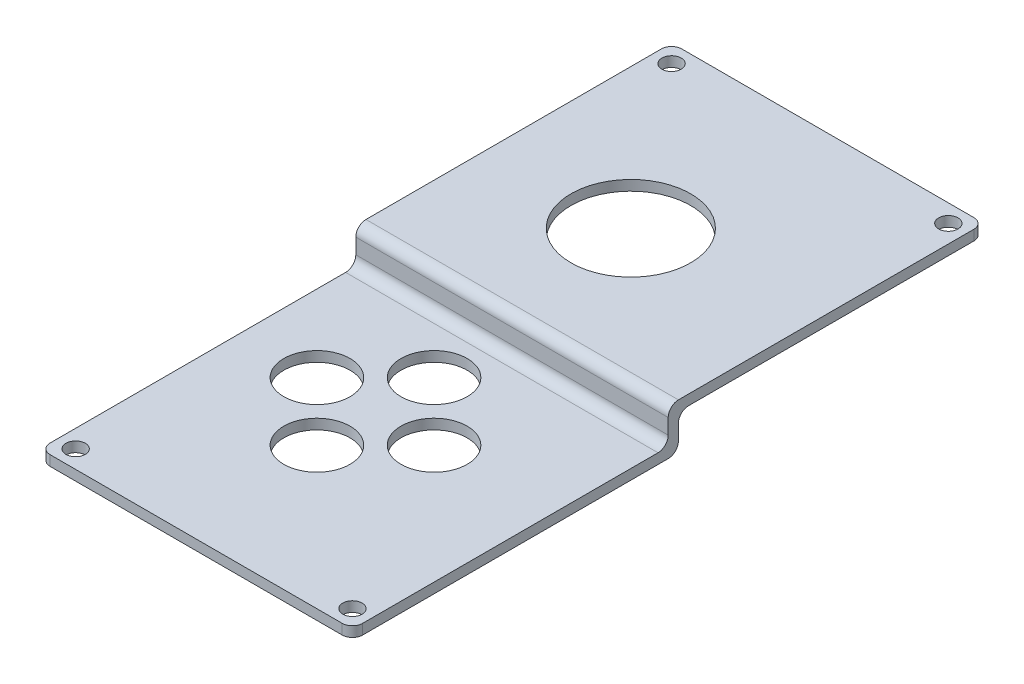
SolidWorks part; units mm, degrees
ref_plane "Front Plane" through (0, 0, 0) normal (0, 0, 1) x (1, 0, 0)
ref_plane "Top Plane" through (0, 0, 0) normal (0, 1, 0) x (1, 0, 0)
ref_plane "Right Plane" through (0, 0, 0) normal (1, 0, 0) x (0, 0, -1)
sketch "Sketch2" plane through (0, 0, 0) normal (1, 0, 0) x (0, 0, -1)
  line L0 (0, 0) -> (60, 0)
  line L1 (0, 0) -> (0, -7)
  line L2 (0, -7) -> (-64, -7)
  line L3 (60, 0) -> (60, 2)
  line L4 (60, 2) -> (-2, 2)
  line L5 (-2, 2) -> (-2, -5)
  line L6 (-2, -5) -> (-64, -5)
  line L7 (-64, -5) -> (-64, -7)
  dimension "D1" = 60
  dimension "D2" = 7
  dimension "D3" = 64
  dimension "D4" = 2
  dimension "D5" = 2
  dimension "D6" = 2
extrude "Boss-Extrude1" add sketch "Sketch2" along normal blind 61.34
sketch "Sketch3" plane through (0, 2, 0) normal (0, 1, 0) x (1, 0, 0)
  line L0 (27.5, 60) -> (27.5, 24.5) construction
  line L1 (61.34, 60) -> (0, 60) construction
  line L2 (0, 60) -> (0, -2) construction
  line L3 (0, 56.5) -> (3.5, 56.5) construction
  line L4 (61.34, 56.5) -> (57.84, 56.5) construction
  line L6 (61.34, 60) -> (61.34, -2) construction
  circle A0 centre (27.5, 24.5) radius 11.75
  circle A1 centre (57.84, 56.5) radius 1.9
  circle A2 centre (3.5, 56.5) radius 1.9
  dimension "D3" = 23.5
  dimension "D8" = 3.8
  dimension "D9" = 3.8
  dimension "D1" = 35.5
  dimension "D2" = 27.5
  dimension "D4" = 3.5
  dimension "D5" = 3.5
  dimension "D6" = 3.5
  dimension "D7" = 3.5
sketch "Sketch4" plane through (0, -5, 0) normal (0, 1, 0) x (1, 0, 0)
  line L0 (15.07, -64) -> (15.07, -24.7) construction
  line L1 (61.34, -64) -> (0, -64) construction
  line L2 (15.07, -24.7) -> (0, -24.7) construction
  line L3 (0, -2) -> (0, -64) construction
  line L4 (15.07, -24.7) -> (38.07, -24.7) construction
  line L5 (26.57, -24.7) -> (26.57, -36.2) construction
  line L6 (61.34, -60.5) -> (57.84, -60.5) construction
  line L7 (61.34, -2) -> (61.34, -64) construction
  line L8 (0, -60.5) -> (3.5, -60.5) construction
  line L9 (26.57, -24.7) -> (26.57, -13.2) construction
  circle A0 centre (38.07, -24.7) radius 6.5
  circle A1 centre (26.57, -36.2) radius 6.5
  circle A2 centre (15.07, -24.7) radius 6.5
  circle A3 centre (26.57, -13.2) radius 6.5
  circle A4 centre (57.84, -60.5) radius 1.9
  circle A5 centre (3.5, -60.5) radius 1.9
  dimension "D5" = 13
  dimension "D6" = 13
  dimension "D7" = 13
  dimension "D8" = 13
  dimension "D13" = 3.8
  dimension "D14" = 3.8
  dimension "D1" = 39.3
  dimension "D2" = 15.07
  dimension "D3" = 23
  dimension "D4" = 11.5
  dimension "D9" = 3.5
  dimension "D10" = 3.5
  dimension "D11" = 3.5
  dimension "D12" = 3.5
  dimension "D15" = 11.5
extrude "Cut-Extrude1" cut sketch "Sketch3" against normal through all
extrude "Cut-Extrude2" cut sketch "Sketch4" against normal through all
fillet "Fillet1" radius 2 4 edges at (30.67, 0, 0) (30.67, -7, 0) (30.67, 2, 2) (30.67, -5, 2)
fillet "Fillet3" radius 2 4 edges at (61.34, 1, -60) (61.34, -6, 64) (0, -6, 64) (0, 1, -60)
